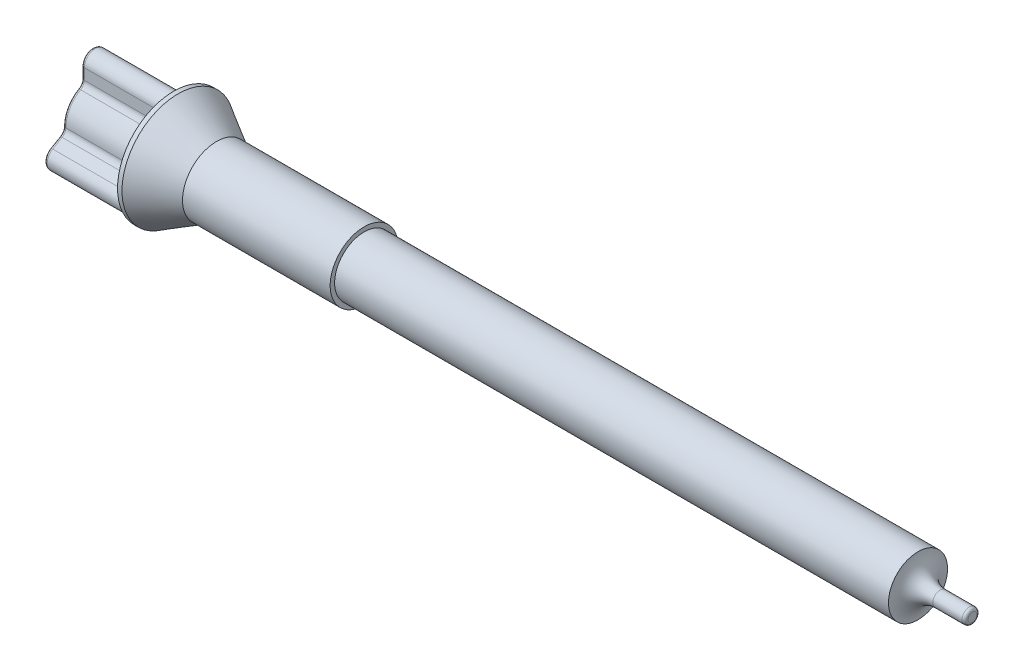
SolidWorks part; units mm, degrees
ref_plane "Front Plane" through (0, 0, 0) normal (0, 0, 1) x (1, 0, 0)
ref_plane "Top Plane" through (0, 0, 0) normal (0, 1, 0) x (1, 0, 0)
ref_plane "Right Plane" through (0, 0, 0) normal (1, 0, 0) x (0, 0, -1)
sketch "Sketch1" plane through (0, 0, 0) normal (0, 0, 1) x (1, 0, 0)
  line L0 (0, 0) -> (0, 1)
  line L1 (0, 1) -> (2.75, 1)
  line L2 (2.75, 1) -> (2.75, 1.9)
  line L3 (2.75, 1.9) -> (2.9, 1.9)
  line L4 (2.9, 1.9) -> (4.199, 1.15)
  line L5 (4.199, 1.15) -> (9.199, 1.15)
  line L6 (9.199, 1.15) -> (9.199, 1)
  line L7 (9.199, 1) -> (27.949, 1)
  line L8 (27.949, 1) -> (27.949, 0)
  line L9 (27.949, 0) -> (0, 0)
  dimension "D1" = 1
  dimension "D2" = 2.75
  dimension "D3" = 0.9
  dimension "D4" = 0.15
  dimension "D5" = 5
  dimension "D6" = 0.15
  dimension "D7" = 1
  dimension "D8" = 18.75
  dimension "D9" = 150
revolve "Revolve1" add sketch "Sketch1" angle 360 about L9
sketch "Sketch2" plane through (0, 0, 0) normal (-1, 0, 0) x (0, 0, 1)
  line L1 (-0.375, 0) -> (0.375, 0)
  line L2 (-0.375, 0) -> (-0.375, 1.45)
  line L3 (-0.375, 1.45) -> (0.375, 1.45) construction
  line L4 (0.375, 0) -> (0.375, 1.45)
  arc A0 (-0.375, 1.45) -> (0.375, 1.45) centre (0, 1.45) cw
  point P4 (0, 0)
  dimension "D1" = 0.75
  dimension "D2" = 1.45
extrude "Boss-Extrude1" add sketch "Sketch2" against normal up to surface (2.75 mm away) up to face at (2.75, 0, -1)
pattern_circular "CirPattern1" count 3 over 360 about axis through (27.949, 0, 0) along (1, 0, 0) of "Boss-Extrude1"
fillet "Fillet1" radius 0.25 9 edges at (1.375, 0.927, -0.375) (1.375, -0.1388, -0.9903) (2.75, 0.5, -0.866) (1.375, -0.7883, 0.6153) (1.375, -0.7883, -0.6153) (2.75, -1, 0) (1.375, -0.1388, 0.9903) (1.375, 0.927, 0.375) (2.75, 0.5, 0.866)
sketch "Sketch3" plane through (27.949, 0, 0) normal (1, 0, 0) x (0, 0, -1)
  circle A0 centre (0, 0) radius 0.25
  dimension "D1" = 0.5
extrude "Boss-Extrude2" add sketch "Sketch3" along normal blind 1.84
fillet "Fillet2" radius 0.75 1 edges at (27.949, 0, -0.25)
fillet "Fillet3" radius 0.1 19 edges at (29.789, 0, -0.25) (0, -0.8325, -0.625) (0, -0.9579, -0.9091) (0, -0.9125, -1.5805) (0, -0.3084, -1.2841) (0, -0.125, -1.0335) (0, 0.5, -0.866) (0, 0.9575, -0.4085) (0, 1.2663, -0.375) (0, 1.825, 0) (0, 1.2663, 0.375) (0, 0.9575, 0.4085) (0, 0.5, 0.866) (0, -0.125, 1.0335) (0, -0.3084, 1.2841) (0, -0.9125, 1.5805) (0, -0.9579, 0.9091) (0, -0.8325, 0.625) (0, -1, 0)
